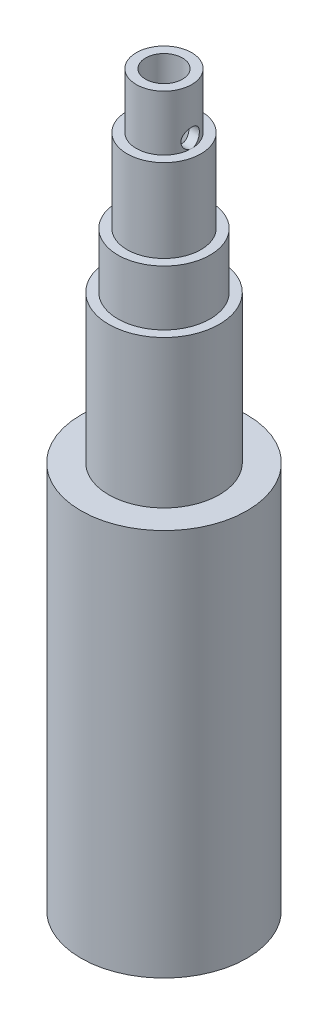
SolidWorks part; units mm, degrees
material "Plain Carbon Steel"
ref_plane "Front Plane" through (0, 0, 0) normal (0, 0, 1) x (1, 0, 0)
ref_plane "Top Plane" through (0, 0, 0) normal (0, 1, 0) x (1, 0, 0)
ref_plane "Right Plane" through (0, 0, 0) normal (1, 0, 0) x (0, 0, -1)
sketch "Sketch1" plane through (0, 0, 0) normal (0, 1, 0) x (1, 0, 0)
  circle A0 centre (0, 0) radius 9
  dimension "D1" = 18
extrude "base section" add sketch "Sketch1" along normal blind 42
sketch "Sketch2" plane through (0, 42, 0) normal (0, 1, 0) x (1, 0, 0)
  circle A0 centre (0, 0) radius 6
  dimension "D1" = 12
extrude "second section" add sketch "Sketch2" along normal blind 16
sketch "Sketch3" plane through (0, 58, 0) normal (0, 1, 0) x (1, 0, 0)
  circle A0 centre (0, 0) radius 5
  dimension "D1" = 10
extrude "bearing section" add sketch "Sketch3" along normal blind 6
sketch "Sketch4" plane through (0, 64, 0) normal (0, 1, 0) x (1, 0, 0)
  circle A0 centre (0, 0) radius 4
  dimension "D1" = 8
extrude "seal section" add sketch "Sketch4" along normal blind 9
sketch "Sketch5" plane through (0, 73, 0) normal (0, 1, 0) x (1, 0, 0)
  circle A0 centre (0, 0) radius 3
  dimension "D1" = 6
extrude "impeller section" add sketch "Sketch5" along normal blind 6
sketch "Sketch6" plane through (0, 79, 0) normal (0, 1, 0) x (1, 0, 0)
  circle A0 centre (0, 0) radius 2
  dimension "D1" = 4
extrude "impeller screw hole" cut sketch "Sketch6" against normal blind 10
sketch "Sketch7" plane through (0, 0, 0) normal (0, -1, 0) x (-1, 0, 0)
  circle A0 centre (0, 0) radius 4
  dimension "D1" = 8
extrude "motor shaft hole" cut sketch "Sketch7" against normal blind 32
sketch "Sketch8" plane through (0, 0, 0) normal (1, 0, 0) x (0, 0, -1)
  line L0 (0, 79) -> (0, 73) construction
  line L1 (3, 79) -> (-3, 79) construction
  line L2 (4, 73) -> (-4, 73) construction
  circle A0 centre (0, 74) radius 1
  dimension "D1" = 2
extrude "impeller dowel hole" cut sketch "Sketch8" against normal blind 10 and the other way blind 10
sketch "Sketch9" plane through (0, 0, 0) normal (1, 0, 0) x (0, 0, -1)
  line L0 (0, 32) -> (0, 0) construction
  line L1 (-4, 32) -> (4, 32) construction
  circle A0 centre (0, 29) radius 3
  circle A1 centre (0, 18.3333) radius 3
  dimension "D1" = 6
  dimension "D2" = 10.6667
extrude "set screw holes" cut sketch "Sketch9" against normal blind 20
equation "\"D1@Sketch1\"=\"coupler shaft base diameter\""
equation "\"bearing OD\" = 20mm"
equation "\"bearing outer race thickness\"= 1mm"
equation "\"bearing ID\"= 10mm"
equation "\"bearing depth\"= 6mm"
equation "\"bearing inner race thickness\"= 1mm"
equation "\"seal OD\" = 20mm"
equation "\"seal ID\"= 8mm"
equation "\"seal depth\"= 6mm"
equation "\"impeller base outer diameter\"= \"d2\""
equation "\"impeller base outer thickness\"= 2mm"
equation "\"impeller base center thickness\"= \"impeller base outer thickness\""
equation "\"impeller number of vanes\"= \"z\""
equation "\"impeller vane inner height\"= \"b1\""
equation "\"impeller primary vane opening diamater\"= \"de\""
equation "\"impeller vane inner thickness\"= \"s\""
equation "\"impeller vane outer thickness\"= \"s\""
equation "\"impeller primary vane entrance angle\"= 0deg"
equation "\"impeller secondary vane entrance angle\"= 0deg"
equation "\"impeller secondary vane opening diameter\"= \"de\""
equation "\"motor to housing distance\"= 60mm"
equation "\"motor mount pattern diameter\"= 30mm"
equation "\"motor mount coupler shaft hole diameter\"= \"coupler shaft base diameter\"+ 4mm"
equation "\"motor mount to housing m8 screw hole diameter\"= 8.5mm"
equation "\"motor mount to housing m8 screw post radius\"= ( 3 * \"motor mount to housing m8 screw hole diameter\" ) / 2"
equation "\"motor mount to housing m8 pattern diameter\"= 100mm"
equation "\"motor mount to housing m4 screw hole diamater\"= 4mm"
equation "\"motor mount to housing m4 head diameter\"= 7.25mm"
equation "\"motor mount to housing m4 head depth\"= 4mm"
equation "\"motor mount plate thickness\"= 6mm + \"motor mount to housing m4 head depth\""
equation "\"motor shaft pride\"= 32mm"
equation "\"motor shaft flat section length from tip\"= 25.7mm"
equation "\"motor shaft bore end clearance\"= 2mm"
equation "\"motor mount shaft hole depth\"= \"motor shaft pride\""
equation "\"coupler shaft set screw drill hole diameter\"= 6mm"
equation "\"coupler shaft motor shaft hole diameter\"= 8mm"
equation "\"coupler shaft base diameter\"= 18mm"
equation "\"coupler shaft base length\"= \"motor mount shaft hole depth\" + 10mm"
equation "\"coupler shaft second section diameter\"= \"bearing ID\" + \"bearing inner race thickness\" * 2"
equation "\"coupler shaft third section diamater\"= \"bearing ID\""
equation "\"coupler shaft second section length\"= \"motor to housing distance\" -  \"coupler shaft base length\" - 2mm"
equation "\"coupler shaft set screw 1 distance\"= \"motor mount shaft hole depth\" / 3"
equation "\"coupler shaft set screw 2 distance\"= \"motor mount shaft hole depth\" * 4 / 5"
equation "\"housing bearing seat lip thickness\" = 2mm"
equation "\"housing base thickness\"= \"housing bearing seat lip thickness\" + \"seal depth\" + \"bearing depth\""
equation "\"housing top impeller vertical clearance\"= .5mm"
equation "\"housing top impeller horizontal clearance\"= .5mm"
equation "\"housing top impeller bottom clearance\"= 1mm"
equation "\"housing top impeller cavity height\"= \"housing top impeller bottom clearance\" + \"impeller base center thickness\" + \"impeller vane inner height\" + \"housing top impeller vertical clearance\""
equation "\"housing top impeller cavity diameter\"= 2 * \"housing top impeller horizontal clearance\" + \"impeller base outer diameter\""
equation "\"housing top impeller cavity tip height\"= \"housing top impeller bottom clearance\" + \"housing top impeller vertical clearance\" + \"impeller base outer thickness\" + \"impeller vane outer height\""
equation "\"housing top entrance OD\"= 20mm"
equation "\"housing top exit OD\"= \"d_exit\""
equation "\"housing top o-ring channel height\"= 1.5mm"
equation "\"housing top o ring channel width\"= 1.5mm"
equation "\"housing top threaded inlet depth\"= 8mm"
equation "\"housing top total thickness\"= \"housing top threaded inlet depth\" + \"housing top impeller cavity height\""
equation "\"housing top total width\"= 10mm"
equation "\"housing top exit threaded diameter\"= 8mm"
equation "\"housing top exit threaded depth\"= 8mm"
equation "\"coupler shaft third section length\"= \"bearing depth\""
equation "\"coupler shaft seal section diameter\" = \"seal ID\""
equation "\"coupler shaft seal section length\" = \"housing base thickness\"+\"housing top impeller bottom clearance\"-\"bearing depth\""
equation "\"coupler shaft impeller section diameter\" = 6mm"
equation "\"coupler shaft impeller section length\" = \"impeller boss depth\"+\"impeller base center thickness\" - 1mm"
equation "\"D1@base section\" = \"coupler shaft base length\""
equation "\"D1@Sketch2\"=\"coupler shaft second section diameter\""
equation "\"D1@second section\" = \"coupler shaft second section length\""
equation "\"D1@Sketch3\"=\"coupler shaft third section diamater\""
equation "\"D1@bearing section\" = \"coupler shaft third section length\""
equation "\"D1@Sketch4\"=\"coupler shaft seal section diameter\""
equation "\"D1@seal section\" = \"coupler shaft seal section length\""
equation "\"D1@Sketch5\"=\"coupler shaft impeller section diameter\""
equation "\"D1@impeller section\" = \"coupler shaft impeller section length\""
equation "\"coupler shaft impeller screw hole diameter\" = \"motor mount to housing m4 screw hole diamater\""
equation "\"coupler shaft impeller screw hole depth\" = 10mm"
equation "\"D1@Sketch6\"=\"coupler shaft impeller screw hole diameter\""
equation "\"D1@impeller screw hole\" = \"coupler shaft impeller screw hole depth\""
equation "\"D1@Sketch7\"=\"coupler shaft motor shaft hole diameter\""
equation "\"D1@motor shaft hole\" = \"motor mount shaft hole depth\""
equation "\"impeller vane outer height\"= \"b2\""
equation "\"impeller bolt surface height\" = 5mm"
equation "\"impeller bolt surface diameter\" = 8mm"
equation "\"housing top o-ring circumference\" = 250mm"
equation "\"housing top o-ring radius\" = (\"housing top o-ring circumference\")/(2*3.14)"
equation "\"coupler shaft to motor clearance\" = 2mm"
equation "\"impeller dowel diameter\" = 2mm"
equation "\"impeller dowel length\" = 2mm*2 + \"coupler shaft impeller section diameter\""
equation "\"D1@Sketch8\"=\"impeller dowel diameter\""
equation "\"D1@Sketch9\"=\"coupler shaft set screw drill hole diameter\""
equation "\"D2@Sketch9\"=\"coupler shaft set screw 1 distance\""
equation "\"impeller boss depth\" = 5mm"
equation "\"impeller boss diameter\" = \"coupler shaft impeller section diameter\"+2*5mm"
